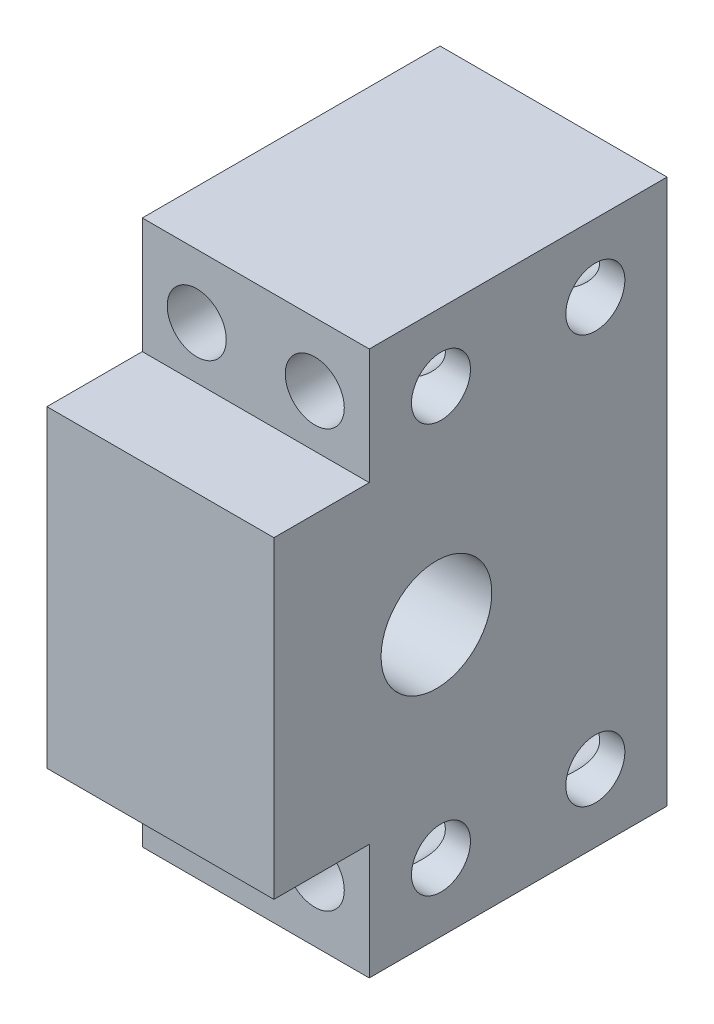
SolidWorks part; units mm, degrees
ref_plane "Front Plane" through (0, 0, 0) normal (0, 0, 1) x (1, 0, 0)
ref_plane "Top Plane" through (0, 0, 0) normal (0, 1, 0) x (1, 0, 0)
ref_plane "Right Plane" through (0, 0, 0) normal (1, 0, 0) x (0, 0, -1)
sketch "Sketch1" plane through (0, 0, 0) normal (0, 0, 1) x (1, 0, 0)
  line L1 (311.275, -30) -> (336.275, -30)
  line L2 (311.275, -30) -> (311.275, 30)
  line L3 (311.275, 30) -> (336.275, 30)
  line L4 (336.275, -30) -> (336.275, 30)
  line L5 (311.275, -30) -> (336.275, 30) construction
  line L6 (311.275, 30) -> (336.275, -30) construction
  line L8 (304.725, -30) -> (342.825, -30) construction
  line L9 (311.275, -17.25) -> (336.275, -17.25)
  line L10 (311.275, -17.25) -> (311.275, 17.25)
  line L11 (311.275, 17.25) -> (336.275, 17.25)
  line L12 (336.275, -17.25) -> (336.275, 17.25)
  line L13 (311.275, -17.25) -> (336.275, 17.25) construction
  line L14 (311.275, 17.25) -> (336.275, -17.25) construction
  line L15 (304.725, 30) -> (342.825, -30) construction
  circle A0 centre (330.275, -23) radius 2.1 construction
  circle A1 centre (317.275, -23) radius 2.1 construction
  circle A2 centre (330.275, 23) radius 2.1 construction
  circle A3 centre (317.275, 23) radius 2.1 construction
  circle A4 centre (330.275, -23) radius 2.1 construction
  circle A5 centre (317.275, -23) radius 2.1 construction
  circle A6 centre (330.275, 23) radius 2.1 construction
  circle A7 centre (317.275, 23) radius 2.1 construction
  circle A8 centre (317.275, 23) radius 3.25
  circle A9 centre (330.275, 23) radius 3.25
  circle A10 centre (317.275, -23) radius 3.25
  circle A11 centre (330.275, -23) radius 3.25
  point P20 (323.775, 0)
  point P25 (0, 0)
  point P28 (317.225, 0)
  point P35 (0, 0)
  point P37 (323.775, 0)
  dimension "D1" = 6.5
  dimension "D2" = 25
  dimension "D3" = 34.5
extrude "Boss-Extrude1" add sketch "Sketch1" along normal blind 32.8 contours L11 L2 L9 L4 | L2 L11 L4 L3 A9 A8 | L9 L2 L1 L4 A11 A10 region at (323.775, -23.7893, 0) region at (323.775, 0, 0) region at (323.775, 23.7893, 0)
extrude "Boss-Extrude2" add sketch "Sketch1<3>" along normal blind 10.5 from surface contours L11 L2 L9 L4 region at (323.775, 0, 0) starting at face at (323.775, 0, 32.8)
sketch "Sketch1<3>" plane through (0, 0, 0) normal (0, 0, 1) x (1, 0, 0) same geometry as "Sketch1"
sketch "Sketch2" plane through (0, 0, 0) normal (1, 0, 0) x (0, 0, -1)
  line L0 (-24.9, 22.5) -> (-7.9, 22.5) construction
  line L1 (-24.9, 22.5) -> (-24.9, -22.5) construction
  line L2 (0, 0) -> (-32.8, 0) construction
  line L3 (0, -30) -> (0, 30) construction
  line L4 (-32.8, 17.25) -> (-32.8, 30) construction
  line L7 (-43.3, 17.25) -> (-43.3, -17.25) construction
  circle A0 centre (-24.9, 22.5) radius 3.25
  circle A1 centre (-7.9, 22.5) radius 3.25
  circle A2 centre (-7.9, -22.5) radius 3.25
  circle A3 centre (-24.9, -22.5) radius 3.25
  circle A4 centre (-25.4, 0) radius 6.1
  point P2 (-24.9, 0)
  point P21 (-16.4, 0)
  point P22 (-16.4, 22.5)
  dimension "D1" = 2
  dimension "D6" = 6.5
  dimension "D3" = 12.2
  dimension "D7" = 11.8
  dimension "D4" = 17
  dimension "D5" = 45
  dimension "D2" = 2
extrude "Cut-Extrude1" cut sketch "Sketch2" along normal up to surface (336.275 mm away) up to face at (336.275, 0, 27.225)
